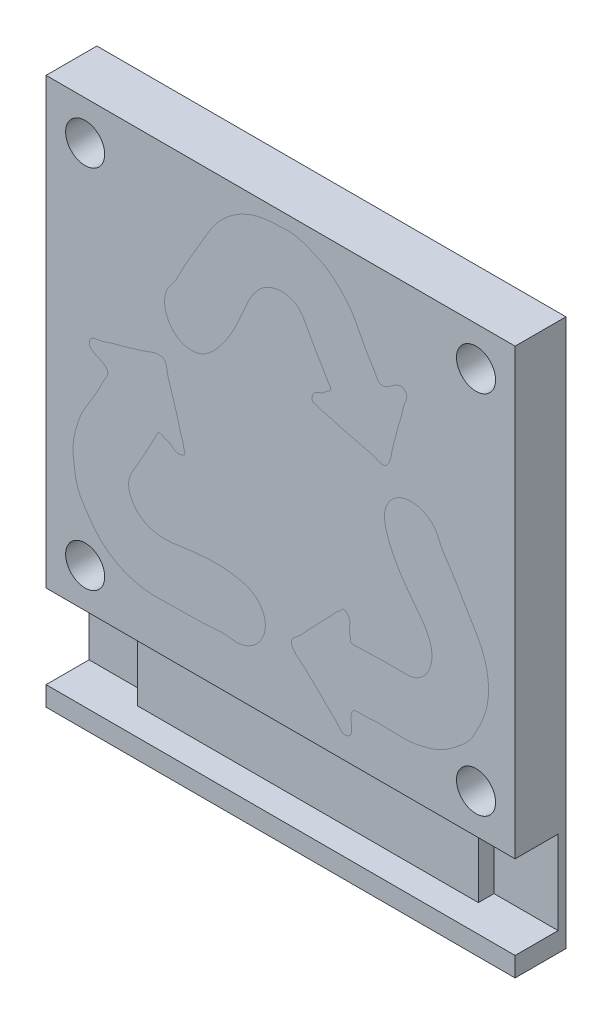
SolidWorks part; units mm, degrees
ref_plane "Front Plane" through (0, 0, 0) normal (0, 0, 1) x (1, 0, 0)
ref_plane "Top Plane" through (0, 0, 0) normal (0, 1, 0) x (1, 0, 0)
ref_plane "Right Plane" through (0, 0, 0) normal (1, 0, 0) x (0, 0, -1)
sketch "Sketch1" plane through (0, 0, 0) normal (0, 0, 1) x (1, 0, 0)
  line L0 (137.9686, 390.3403) -> (878.5926, 390.3403) construction
  line L1 (-39.205, 61.8798) -> (20.795, 61.8798)
  line L2 (-39.205, 61.8798) -> (-39.205, -8.1202)
  line L3 (-39.205, -8.1202) -> (20.795, -8.1202)
  line L4 (20.795, 61.8798) -> (20.795, -8.1202)
  line L5 (-9.205, -8.1202) -> (-9.205, 61.8798) construction
  line L6 (-9.205, 5.0798) -> (-9.205, -5.6202) construction
  line L7 (16.595, 5.0798) -> (-35.005, 5.0798)
  line L8 (16.595, 5.0798) -> (16.595, -5.6202)
  line L9 (16.595, -5.6202) -> (-35.005, -5.6202)
  line L10 (-35.005, 5.0798) -> (-35.005, -5.6202)
  line L12 (-35.005, -5.6202) -> (-31.005, -5.6202)
  line L13 (-35.005, -5.6202) -> (-35.005, 5.0798)
  line L14 (-35.005, 5.0798) -> (-31.005, 5.0798)
  line L15 (-31.005, -5.6202) -> (-31.005, 5.0798)
  line L16 (16.595, -5.6202) -> (12.595, -5.6202)
  line L17 (16.595, -5.6202) -> (16.595, 5.0798)
  line L18 (16.595, 5.0798) -> (12.595, 5.0798)
  line L19 (12.595, -5.6202) -> (12.595, 5.0798)
  line L20 (-35.005, 5.0798) -> (-39.205, 5.0798)
  line L21 (-35.005, 5.0798) -> (-35.005, -5.6202)
  line L22 (-35.005, -5.6202) -> (-39.205, -5.6202)
  line L23 (-39.205, 5.0798) -> (-39.205, -5.6202)
  line L24 (16.595, 5.0798) -> (20.795, 5.0798)
  line L25 (16.595, 5.0798) -> (16.595, -5.6202)
  line L26 (16.595, -5.6202) -> (20.795, -5.6202)
  line L27 (20.795, 5.0798) -> (20.795, -5.6202)
  spline S0 degree 3 poles (-22.5475, 47.4452) (-23.762, 46.1779) (-24.3789, 43.7895) (-22.8702, 40.9283) (-19.5004, 40.4419) (-16.3774, 43.2656) (-14.2795, 47.37) (-12.5291, 52.0388) (-9.1817, 53.306) (-6.7496, 52.521) (-5.7492, 50.437) (-4.4677, 48.2197) (-3.5742, 46.6813) (-2.5961, 45.1378) (-3.3272, 44.8941) (-3.682, 44.411) (-4.335, 44.1751) (-5.0802, 43.8692) (-5.3524, 42.7286) (-4.6109, 42.6899) (-4.0981, 42.3769) (-3.2192, 42.2668) (-2.2079, 41.8949) (-1.0408, 41.6232) (0.1728, 41.2811) (1.4949, 40.9948) (2.7612, 40.6975) (4.0193, 40.0359) (4.8678, 41.0713) (4.9874, 42.4046) (5.4255, 43.8405) (5.7643, 45.3973) (6.2893, 46.7855) (6.4732, 48.2556) (7.2296, 49.4984) (6.3268, 50.262) (5.5365, 49.963) (4.9187, 49.516) (4.2806, 49.0532) (3.3367, 48.9621) (2.8931, 50.0468) (2.1293, 51.1277) (1.3833, 52.4885) (0.6704, 53.8686) (0.0032, 55.2009) (-1.0132, 56.4366) (-2.1473, 57.6484) (-3.48, 58.6078) (-4.8088, 59.191) (-6.1593, 59.793) (-7.6977, 60.1977) (-9.3988, 60.1026) (-11.2043, 60.0212) (-13.1021, 59.5782) (-14.8828, 58.6917) (-16.4354, 57.4791) (-17.731, 56.0923) (-18.77, 54.3277) (-19.7563, 52.621) (-20.8391, 50.789) (-21.8127, 49.106) (-22.5475, 47.4452) (-23.762, 46.1779) (-24.3789, 43.7895) knots -0.053289 -0.029892 -0.013186 0 0.021391 0.05573 0.081326 0.110479 0.172031 0.221619 0.247569 0.27037 0.289521 0.313837 0.344637 0.350629 0.357164 0.361728 0.368708 0.376673 0.386302 0.39019 0.395738 0.404312 0.415754 0.427728 0.439702 0.453255 0.467208 0.480476 0.487516 0.502252 0.52004 0.531767 0.549572 0.563172 0.577277 0.584796 0.591055 0.600466 0.607749 0.614456 0.624899 0.637303 0.655447 0.670099 0.683552 0.699384 0.717269 0.732642 0.747617 0.760143 0.776501 0.794085 0.810269 0.830075 0.851297 0.868642 0.888248 0.907092 0.929113 0.946711 0.970108 0.986814 1 1.021391 1.05573 1.081326 only from (-23.4936, 46.3306) to (-23.4936, 46.3306)
  spline S1 degree 3 poles (11.331, 34.7513) (10.8116, 36.4279) (9.0219, 38.1256) (5.788, 38.1934) (3.7286, 35.4821) (4.6839, 31.3816) (7.2563, 27.5567) (10.4908, 23.762) (9.9759, 20.22) (8.1101, 18.4735) (5.8025, 18.6091) (3.2419, 18.5635) (1.4632, 18.528) (-0.361, 18.4209) (-0.2197, 19.1786) (-0.4701, 19.7231) (-0.3598, 20.4086) (-0.266, 21.2086) (-1.1316, 21.9998) (-1.525, 21.37) (-2.0473, 21.0733) (-2.5698, 20.358) (-3.3855, 19.6539) (-4.1889, 18.7649) (-5.0766, 17.8694) (-5.9681, 16.852) (-6.842, 15.8886) (-8.0307, 15.1091) (-7.5366, 13.8649) (-6.4285, 13.1138) (-5.3851, 12.0345) (-4.1878, 10.9833) (-3.2284, 9.8511) (-2.0318, 8.9773) (-1.3116, 7.7133) (-0.2061, 8.1326) (-0.0843, 8.9687) (-0.1758, 9.7258) (-0.2711, 10.5083) (0.1069, 11.378) (1.2707, 11.2399) (2.5864, 11.3838) (4.1383, 11.3765) (5.691, 11.3308) (7.1796, 11.2683) (8.7532, 11.5581) (10.3628, 11.9623) (11.8482, 12.6627) (13.0025, 13.542) (14.1838, 14.4312) (15.2837, 15.5804) (16.0254, 17.1144) (16.8297, 18.7328) (17.3624, 20.6074) (17.4506, 22.5946) (17.1428, 24.5405) (16.5582, 26.346) (15.5187, 28.1103) (14.5043, 29.8004) (13.4271, 31.6358) (12.4273, 33.3033) (11.331, 34.7513) (10.8116, 36.4279) (9.0219, 38.1256) knots -0.053289 -0.029892 -0.013186 0 0.021391 0.05573 0.081326 0.110479 0.172031 0.221619 0.247569 0.27037 0.289521 0.313837 0.344637 0.350629 0.357164 0.361728 0.368708 0.376673 0.386302 0.39019 0.395738 0.404312 0.415754 0.427728 0.439702 0.453255 0.467208 0.480476 0.487516 0.502252 0.52004 0.531767 0.549572 0.563172 0.577277 0.584796 0.591055 0.600466 0.607749 0.614456 0.624899 0.637303 0.655447 0.670099 0.683552 0.699384 0.717269 0.732642 0.747617 0.760143 0.776501 0.794085 0.810269 0.830075 0.851297 0.868642 0.888248 0.907092 0.929113 0.946711 0.970108 0.986814 1 1.021391 1.05573 1.081326 only from (10.815, 36.1192) to (10.815, 36.1192)
  spline S2 degree 3 poles (-16.3765, 11.4911) (-14.663, 11.1103) (-12.3012, 11.822) (-10.6379, 14.5962) (-11.9703, 17.7294) (-16.0046, 18.9342) (-20.6018, 18.5983) (-25.5012, 17.6724) (-28.3212, 19.8767) (-28.9119, 22.3631) (-27.6494, 24.2995) (-26.4187, 26.5454) (-25.5671, 28.1074) (-24.755, 29.7444) (-24.1673, 29.2458) (-23.5702, 29.1931) (-23.0298, 28.7573) (-22.3817, 28.2789) (-21.2653, 28.638) (-21.617, 29.292) (-21.6155, 29.8927) (-21.9774, 30.7013) (-22.184, 31.7588) (-22.5573, 32.8974) (-22.8945, 34.1125) (-23.3356, 35.3912) (-23.7385, 36.6279) (-23.8255, 38.0468) (-25.151, 38.2349) (-26.3529, 37.6455) (-27.8077, 37.275) (-29.3143, 36.757) (-30.7734, 36.4856) (-32.1257, 35.8801) (-33.5805, 35.8819) (-33.7649, 34.714) (-33.0993, 34.1934) (-32.3966, 33.8973) (-31.6699, 33.5919) (-31.1023, 32.8322) (-31.7995, 31.8902) (-32.3273, 30.6764) (-33.1036, 29.3327) (-33.9136, 28.0072) (-34.7064, 26.7457) (-35.2354, 25.2356) (-35.683, 23.6375) (-35.8118, 22.0003) (-35.6209, 20.5618) (-35.4349, 19.095) (-34.9828, 17.5699) (-34.0189, 16.1649) (-33.0126, 14.6636) (-31.6493, 13.2711) (-29.9676, 12.2087) (-28.1254, 11.5106) (-26.2677, 11.1225) (-24.2201, 11.1497) (-22.2494, 11.192) (-20.1214, 11.2168) (-18.1776, 11.2575) (-16.3765, 11.4911) (-14.663, 11.1103) (-12.3012, 11.822) knots -0.053289 -0.029892 -0.013186 0 0.021391 0.05573 0.081326 0.110479 0.172031 0.221619 0.247569 0.27037 0.289521 0.313837 0.344637 0.350629 0.357164 0.361728 0.368708 0.376673 0.386302 0.39019 0.395738 0.404312 0.415754 0.427728 0.439702 0.453255 0.467208 0.480476 0.487516 0.502252 0.52004 0.531767 0.549572 0.563172 0.577277 0.584796 0.591055 0.600466 0.607749 0.614456 0.624899 0.637303 0.655447 0.670099 0.683552 0.699384 0.717269 0.732642 0.747617 0.760143 0.776501 0.794085 0.810269 0.830075 0.851297 0.868642 0.888248 0.907092 0.929113 0.946711 0.970108 0.986814 1 1.021391 1.05573 1.081326 only from (-14.9328, 11.2605) to (-14.9328, 11.2605)
  dimension "D1" = 70
  dimension "D2" = 60
  dimension "D3" = 10.7
  dimension "D4" = 51.6
  dimension "D5" = 2.5
  dimension "D6" = 4
  dimension "D7" = 4
extrude "Back Plate" add sketch "Sketch1" along normal blind 1 contours L7 L24 L4 L1 L2 L20 S2 S1 S0 | L9 L19 L7 L15 | L9 L15 L7 L10 | L22 L10 L20 L2 | L26 L9 L22 L2 L3 L4 | L19 L9 L8 L7 | L8 L26 L4 L24 region at (-9.211, 34.1374, 0) region at (-37.105, -0.2702, 0) region at (18.695, -0.2702, 0) region at (-9.205, -6.8702, 0) region at (-33.005, -0.2702, 0) region at (14.595, -0.2702, 0) region at (-9.205, -0.2702, 0)
extrude "Neopixel Back" add sketch "Sketch1<4>" along normal blind 3 contours L9 L19 L7 L15 region at (-9.205, -0.2702, 0)
sketch "Sketch1<4>" plane through (0, 0, 0) normal (0, 0, 1) x (1, 0, 0) same geometry as "Sketch1"
extrude "Main Color" add sketch "Sketch1<5>" along normal blind 6.5 contours L7 L24 L4 L1 L2 L20 S2 S1 S0 | L26 L9 L22 L2 L3 L4 region at (-9.211, 34.1374, 0) region at (-9.205, -6.8702, 0)
sketch "Sketch1<5>" plane through (0, 0, 0) normal (0, 0, 1) x (1, 0, 0) same geometry as "Sketch1"
extrude "Highlight Color" add sketch "Sketch1<6>" along normal blind 6.5 separate body contours S2 | S0 | S1 region at (4.5796, 41.8819, 0) region at (-6.6723, 13.743, 0) region at (-25.6953, 37.5704, 0)
sketch "Sketch1<6>" plane through (0, 0, 0) normal (0, 0, 1) x (1, 0, 0) same geometry as "Sketch1"
sketch "Sketch2" plane through (0, 0, 6.5) normal (0, 0, 1) x (1, 0, 0)
  line L0 (-9.205, 61.8798) -> (-9.205, 5.0798) construction
  line L1 (-39.205, 61.8798) -> (20.795, 61.8798) construction
  line L2 (20.795, 5.0798) -> (-39.205, 5.0798) construction
  line L3 (-39.205, 33.4798) -> (20.795, 33.4798) construction
  line L4 (-39.205, 61.8798) -> (-39.205, 5.0798) construction
  line L5 (20.795, 61.8798) -> (20.795, 5.0798) construction
  circle A0 centre (-34.205, 56.8798) radius 2.5
  circle A1 centre (15.795, 56.8798) radius 2.5
  circle A2 centre (-34.205, 10.0798) radius 2.5
  circle A3 centre (15.795, 10.0798) radius 2.5
  dimension "D1" = 5
  dimension "D2" = 5
  dimension "D3" = 5
extrude "Mounting Holes" cut sketch "Sketch2" against normal blind 6.5
